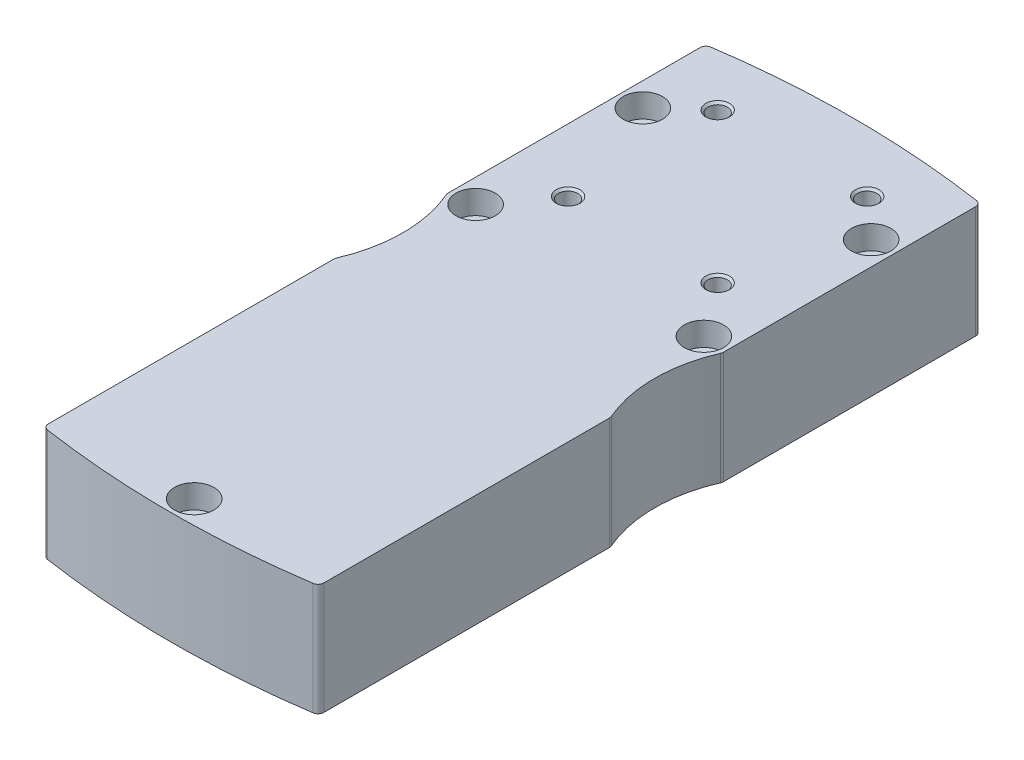
SolidWorks part; units mm, degrees
ref_plane "Front Plane" through (0, 0, 0) normal (0, 0, 1) x (1, 0, 0)
ref_plane "Top Plane" through (0, 0, 0) normal (0, 1, 0) x (1, 0, 0)
ref_plane "Right Plane" through (0, 0, 0) normal (1, 0, 0) x (0, 0, -1)
sketch "Sketch1" plane through (0, 0, 0) normal (0, 1, 0) x (1, 0, 0)
  line L0 (-35, 76.5086) -> (-35, 3.969)
  line L1 (35, 3.969) -> (35, 76.5086)
  line L2 (35, 105.4914) -> (35, 169.531)
  line L3 (-35, 169.531) -> (-35, 105.4914)
  arc A0 (-35, 3.969) -> (-33.7199, 2.4852) centre (-33.5, 3.969) ccw
  arc A1 (-33.7199, 2.4852) -> (33.7199, 2.4852) centre (0, 230) ccw
  arc A2 (33.7199, 2.4852) -> (35, 3.969) centre (33.5, 3.969) ccw
  arc A3 (35, 76.5086) -> (34.8767, 77.1042) centre (33.5, 76.5086) ccw
  arc A4 (34.8767, 77.1042) -> (34.8767, 104.8958) centre (67, 91) cw
  arc A5 (34.8767, 104.8958) -> (35, 105.4914) centre (33.5, 105.4914) ccw
  arc A6 (35, 169.531) -> (33.7199, 171.0148) centre (33.5, 169.531) ccw
  arc A7 (33.7199, 171.0148) -> (-33.7199, 171.0148) centre (0, -56.5) ccw
  arc A8 (-33.7199, 171.0148) -> (-35, 169.531) centre (-33.5, 169.531) ccw
  arc A9 (-35, 105.4914) -> (-34.8767, 104.8958) centre (-33.5, 105.4914) ccw
  arc A10 (-34.8767, 104.8958) -> (-34.8767, 77.1042) centre (-67, 91) cw
  arc A11 (-34.8767, 77.1042) -> (-35, 76.5086) centre (-33.5, 76.5086) ccw
extrude "Boss-Extrude1" add sketch "Sketch1" along normal blind 28.5
sketch "Sketch2" plane through (0, 0, 0) normal (0, 1, 0) x (1, 0, 0)
  line L0 (20, 55.5) -> (20, 106.3205)
  line L1 (18.6603, 111.3205) -> (13.3397, 120.5359)
  line L2 (12, 125.5359) -> (12, 147)
  line L3 (-12, 147) -> (-12, 125.5359)
  line L4 (-13.3397, 120.5359) -> (-18.6603, 111.3205)
  line L5 (-20, 106.3205) -> (-20, 55.5)
  arc A0 (-20.7692, 51.6538) -> (20.7692, 51.6538) centre (0, 43) ccw
  arc A1 (20.7692, 51.6538) -> (20, 55.5) centre (30, 55.5) cw
  arc A2 (20, 106.3205) -> (18.6603, 111.3205) centre (10, 106.3205) ccw
  arc A3 (13.3397, 120.5359) -> (12, 125.5359) centre (22, 125.5359) cw
  arc A4 (12, 147) -> (-12, 147) centre (0, 147) ccw
  arc A5 (-12, 125.5359) -> (-13.3397, 120.5359) centre (-22, 125.5359) cw
  arc A6 (-18.6603, 111.3205) -> (-20, 106.3205) centre (-10, 106.3205) ccw
  arc A7 (-20, 55.5) -> (-20.7692, 51.6538) centre (-30, 55.5) cw
extrude "Cut-Extrude1" cut sketch "Sketch2" along normal blind 26.5
sketch "Sketch3" plane through (0, 0, 0) normal (0, 1, 0) x (1, 0, 0)
  arc A0 (-7.9881, 156.2392) -> (7.9881, 156.2392) centre (0, 139) ccw
  arc A1 (7.9881, 156.2392) -> (6.6503, 156.9886) centre (12.1923, 165.3125) cw
  arc A2 (6.6503, 156.9886) -> (-6.6503, 156.9886) centre (0, 147) ccw
  arc A3 (-6.6503, 156.9886) -> (-7.9881, 156.2392) centre (-12.1923, 165.3125) cw
extrude "Cut-Extrude2" cut sketch "Sketch3" along normal blind 8
sketch "Sketch4" plane through (0, 0, 0) normal (0, 1, 0) x (1, 0, 0)
  line L0 (25, 51.4261) -> (25, 130.5739)
  line L1 (-25, 130.5739) -> (-25, 51.4261)
  arc A0 (-25.2778, 49.0856) -> (25.2778, 49.0856) centre (0, 43) ccw
  arc A1 (25.2778, 49.0856) -> (25, 51.4261) centre (35, 51.4261) cw
  arc A2 (25, 130.5739) -> (25.2778, 132.9144) centre (35, 130.5739) cw
  arc A3 (25.2778, 132.9144) -> (-25.2778, 132.9144) centre (0, 139) ccw
  arc A4 (-25.2778, 132.9144) -> (-25, 130.5739) centre (-35, 130.5739) cw
  arc A5 (-25, 51.4261) -> (-25.2778, 49.0856) centre (-35, 51.4261) cw
extrude "Cut-Extrude3" cut sketch "Sketch4" along normal blind 3
sketch "Sketch5" plane through (0, 0, 0) normal (1, 0, 0) x (0, 0, -1)
  line L0 (6, 28.5) -> (11, 28.5)
  line L1 (11, 28.5) -> (11, 22.5)
  line L2 (11, 22.5) -> (8.75, 22.5)
  line L3 (8.75, 22.5) -> (8.75, 0)
  line L4 (8.75, 0) -> (6, 0)
  line L5 (6, 0) -> (6, 28.5)
  line L6 (6, 0) -> (6, 28.5) construction
revolve "Cut-Revolve1" cut sketch "Sketch5" angle 360 about L6 reverse direction yes
ref_plane "Plane1" through (29, 0, 0) normal (1, 0, 0) x (0, 0, -1)
sketch "Sketch6" plane through (29, 0, 0) normal (1, 0, 0) x (0, 0, -1)
  line L0 (106.5, 28.5) -> (111.5, 28.5)
  line L1 (111.5, 28.5) -> (111.5, 22.5)
  line L2 (111.5, 22.5) -> (109.25, 22.5)
  line L3 (109.25, 22.5) -> (109.25, 0)
  line L4 (109.25, 0) -> (106.5, 0)
  line L5 (106.5, 0) -> (106.5, 28.5)
  line L6 (106.5, 0) -> (106.5, 28.5) construction
revolve "Cut-Revolve2" cut sketch "Sketch6" angle 360 about L6 reverse direction yes
sketch "Sketch7" plane through (29, 0, 0) normal (1, 0, 0) x (0, 0, -1)
  line L0 (149, 28.5) -> (154, 28.5)
  line L1 (154, 28.5) -> (154, 22.5)
  line L2 (154, 22.5) -> (151.75, 22.5)
  line L3 (151.75, 22.5) -> (151.75, 0)
  line L4 (151.75, 0) -> (149, 0)
  line L5 (149, 0) -> (149, 28.5)
  line L6 (149, 0) -> (149, 28.5) construction
revolve "Cut-Revolve3" cut sketch "Sketch7" angle 360 about L6 reverse direction yes
ref_plane "Plane2" through (-29, 0, 0) normal (1, 0, 0) x (0, 0, -1)
sketch "Sketch8" plane through (-29, 0, 0) normal (1, 0, 0) x (0, 0, -1)
  line L0 (106.5, 28.5) -> (111.5, 28.5)
  line L1 (111.5, 28.5) -> (111.5, 22.5)
  line L2 (111.5, 22.5) -> (109.25, 22.5)
  line L3 (109.25, 22.5) -> (109.25, 0)
  line L4 (109.25, 0) -> (106.5, 0)
  line L5 (106.5, 0) -> (106.5, 28.5)
  line L6 (106.5, 0) -> (106.5, 28.5) construction
revolve "Cut-Revolve4" cut sketch "Sketch8" angle 360 about L6 reverse direction yes
sketch "Sketch9" plane through (-29, 0, 0) normal (1, 0, 0) x (0, 0, -1)
  line L0 (149, 28.5) -> (154, 28.5)
  line L1 (154, 28.5) -> (154, 22.5)
  line L2 (154, 22.5) -> (151.75, 22.5)
  line L3 (151.75, 22.5) -> (151.75, 0)
  line L4 (151.75, 0) -> (149, 0)
  line L5 (149, 0) -> (149, 28.5)
  line L6 (149, 0) -> (149, 28.5) construction
revolve "Cut-Revolve5" cut sketch "Sketch9" angle 360 about L6 reverse direction yes
ref_plane "Plane3" through (0, 0, -158) normal (0, 0, 1) x (1, 0, 0)
sketch "Sketch10" plane through (0, 0, -158) normal (0, 0, 1) x (1, 0, 0)
  line L0 (19, 28.5) -> (22, 28.5)
  line L1 (22, 28.5) -> (21.4585, 27.9585)
  line L2 (21.4585, 27.9585) -> (21.4585, 12)
  line L3 (21.4585, 12) -> (19, 10.5806)
  line L4 (19, 10.5806) -> (19, 28.5)
  line L5 (19, 10.5806) -> (19, 28.5) construction
revolve "Cut-Revolve6" cut sketch "Sketch10" angle 360 about L5 reverse direction yes
cosmetic thread "Cosmetic Thread1" parameters "D1"=15, "D2"=6
sketch "Sketch11" plane through (0, 0, -158) normal (0, 0, 1) x (1, 0, 0)
  line L0 (-19, 28.5) -> (-16, 28.5)
  line L1 (-16, 28.5) -> (-16.5415, 27.9585)
  line L2 (-16.5415, 27.9585) -> (-16.5415, 12)
  line L3 (-16.5415, 12) -> (-19, 10.5806)
  line L4 (-19, 10.5806) -> (-19, 28.5)
  line L5 (-19, 10.5806) -> (-19, 28.5) construction
revolve "Cut-Revolve7" cut sketch "Sketch11" angle 360 about L5 reverse direction yes
cosmetic thread "Cosmetic Thread2" parameters "D1"=15, "D2"=6
ref_plane "Plane4" through (0, 0, -120) normal (0, 0, 1) x (1, 0, 0)
sketch "Sketch12" plane through (0, 0, -120) normal (0, 0, 1) x (1, 0, 0)
  line L0 (19, 28.5) -> (22, 28.5)
  line L1 (22, 28.5) -> (21.4585, 27.9585)
  line L2 (21.4585, 27.9585) -> (21.4585, 12)
  line L3 (21.4585, 12) -> (19, 10.5806)
  line L4 (19, 10.5806) -> (19, 28.5)
  line L5 (19, 10.5806) -> (19, 28.5) construction
revolve "Cut-Revolve8" cut sketch "Sketch12" angle 360 about L5 reverse direction yes
cosmetic thread "Cosmetic Thread3" parameters "D1"=15, "D2"=6
sketch "Sketch13" plane through (0, 0, -120) normal (0, 0, 1) x (1, 0, 0)
  line L0 (-19, 28.5) -> (-16, 28.5)
  line L1 (-16, 28.5) -> (-16.5415, 27.9585)
  line L2 (-16.5415, 27.9585) -> (-16.5415, 12)
  line L3 (-16.5415, 12) -> (-19, 10.5806)
  line L4 (-19, 10.5806) -> (-19, 28.5)
  line L5 (-19, 10.5806) -> (-19, 28.5) construction
revolve "Cut-Revolve9" cut sketch "Sketch13" angle 360 about L5 reverse direction yes
cosmetic thread "Cosmetic Thread4" parameters "D1"=15, "D2"=6
ref_plane "Plane5" through (0, 22.5, 0) normal (0, 1, 0) x (1, 0, 0)
ref_plane "ANBAU XY" through (0, 0, 0) normal (0, 1, 0) x (1, 0, 0)
ref_plane "ANBAU XZ" through (0, 0, -139) normal (0, 0, 1) x (1, 0, 0)
ref_plane "ANBAU YZ" through (0, 0, 0) normal (1, 0, 0) x (0, 0, -1)
ref_axis "ANBAU X" through (-80.9, 0, -139) along (1, 0, 0)
ref_axis "ANBAU Y" through (0, 0, 50) along (0, 0, -1)
ref_axis "ANBAU Z" through (0, 50, -139) along (0, -1, 0)
sketch3d "ANBAU"
  point P0 (0, 0, -139)
ref_plane "S1 1 XY" through (0, 22.5, 0) normal (0, 1, 0) x (1, 0, 0)
ref_plane "S1 1 XZ" through (0, 0, -149) normal (0, 0, 1) x (1, 0, 0)
ref_plane "S1 1 YZ" through (29, 0, 0) normal (1, 0, 0) x (0, 0, -1)
ref_axis "S1 1 X" through (-80.9, 22.5, -149) along (1, 0, 0)
ref_axis "S1 1 Y" through (29, 22.5, 50) along (0, 0, -1)
ref_axis "S1 1 Z" through (29, 50, -149) along (0, -1, 0)
sketch3d "S1 1"
  point P0 (29, 22.5, -149)
ref_plane "S1 2 XY" through (0, 22.5, 0) normal (0, 1, 0) x (1, 0, 0)
ref_plane "S1 2 XZ" through (0, 0, -106.5) normal (0, 0, 1) x (1, 0, 0)
ref_plane "S1 2 YZ" through (29, 0, 0) normal (1, 0, 0) x (0, 0, -1)
ref_axis "S1 2 X" through (-80.9, 22.5, -106.5) along (1, 0, 0)
ref_axis "S1 2 Y" through (29, 22.5, 50) along (0, 0, -1)
ref_axis "S1 2 Z" through (29, 50, -106.5) along (0, -1, 0)
sketch3d "S1 2"
  point P0 (29, 22.5, -106.5)
ref_plane "S2 1 XY" through (0, 22.5, 0) normal (0, 1, 0) x (1, 0, 0)
ref_plane "S2 1 XZ" through (0, 0, -149) normal (0, 0, 1) x (1, 0, 0)
ref_plane "S2 1 YZ" through (-29, 0, 0) normal (1, 0, 0) x (0, 0, -1)
ref_axis "S2 1 X" through (-80.9, 22.5, -149) along (1, 0, 0)
ref_axis "S2 1 Y" through (-29, 22.5, 50) along (0, 0, -1)
ref_axis "S2 1 Z" through (-29, 50, -149) along (0, -1, 0)
sketch3d "S2 1"
  point P0 (-29, 22.5, -149)
ref_plane "S2 2 XY" through (0, 22.5, 0) normal (0, 1, 0) x (1, 0, 0)
ref_plane "S2 2 XZ" through (0, 0, -106.5) normal (0, 0, 1) x (1, 0, 0)
ref_plane "S2 2 YZ" through (-29, 0, 0) normal (1, 0, 0) x (0, 0, -1)
ref_axis "S2 2 X" through (-80.9, 22.5, -106.5) along (1, 0, 0)
ref_axis "S2 2 Y" through (-29, 22.5, 50) along (0, 0, -1)
ref_axis "S2 2 Z" through (-29, 50, -106.5) along (0, -1, 0)
sketch3d "S2 2"
  point P0 (-29, 22.5, -106.5)
ref_plane "S3 XY" through (0, 22.5, 0) normal (0, 1, 0) x (1, 0, 0)
ref_plane "S3 XZ" through (0, 0, -6) normal (0, 0, 1) x (1, 0, 0)
ref_plane "S3 YZ" through (0, 0, 0) normal (1, 0, 0) x (0, 0, -1)
ref_axis "S3 X" through (-80.9, 22.5, -6) along (1, 0, 0)
ref_axis "S3 Y" through (0, 22.5, 50) along (0, 0, -1)
ref_axis "S3 Z" through (0, 50, -6) along (0, -1, 0)
sketch3d "S3"
  point P0 (0, 22.5, -6)
other "Freeze***"
